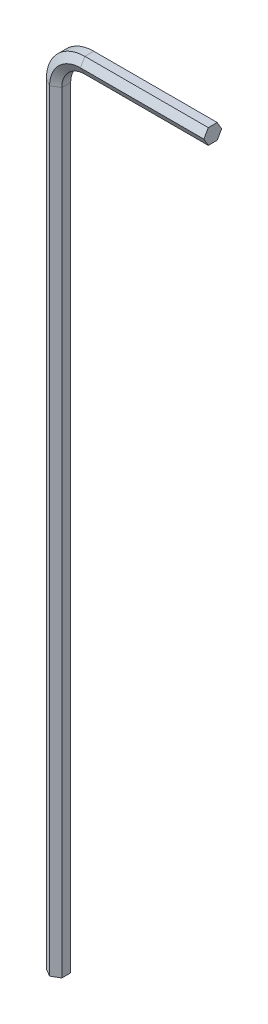
SolidWorks part; units mm, degrees
ref_plane "Front Plane" through (0, 0, 0) normal (0, 0, 1) x (1, 0, 0)
ref_plane "Top Plane" through (0, 0, 0) normal (0, 1, 0) x (1, 0, 0)
ref_plane "Right Plane" through (0, 0, 0) normal (1, 0, 0) x (0, 0, -1)
sketch "Sketch1" plane through (0, 0, 0) normal (0, 0, 1) x (1, 0, 0)
  line L0 (0, 0) -> (-12, 0)
  line L1 (-15, -3) -> (-15, -78)
  arc A0 (-12, 0) -> (-15, -3) centre (-12, -3) ccw
  point P5 (-15, 0)
  dimension "D3" = 3
  dimension "D1" = 15
  dimension "D2" = 78
sketch "6m" plane through (0, 0, 0) normal (1, 0, 0) x (0, 0, -1)
  line L1 (-0.866, 0) -> (-0.433, -0.75)
  line L2 (-0.433, -0.75) -> (0.433, -0.75)
  line L3 (0.433, -0.75) -> (0.866, 0)
  line L4 (0.866, 0) -> (0.433, 0.75)
  line L5 (0.433, 0.75) -> (-0.433, 0.75)
  line L6 (-0.433, 0.75) -> (-0.866, 0)
  circle A0 centre (0, 0) radius 0.75 construction
  dimension "D1" = 1.5
sweep "6mm" add profiles "6m" path "Sketch1"
ref_plane "Plane1" through (-3.75, 0, -6.4952) normal (0.5, 0, 0.866) x (0.866, 0, -0.5)
ref_plane "Plane2" through (-3.75, 0, 6.4952) normal (-0.5, 0, 0.866) x (0.866, 0, 0.5)
ref_axis "Axis1" through (-15, -81.75, 0) along (0, 1, 0)
